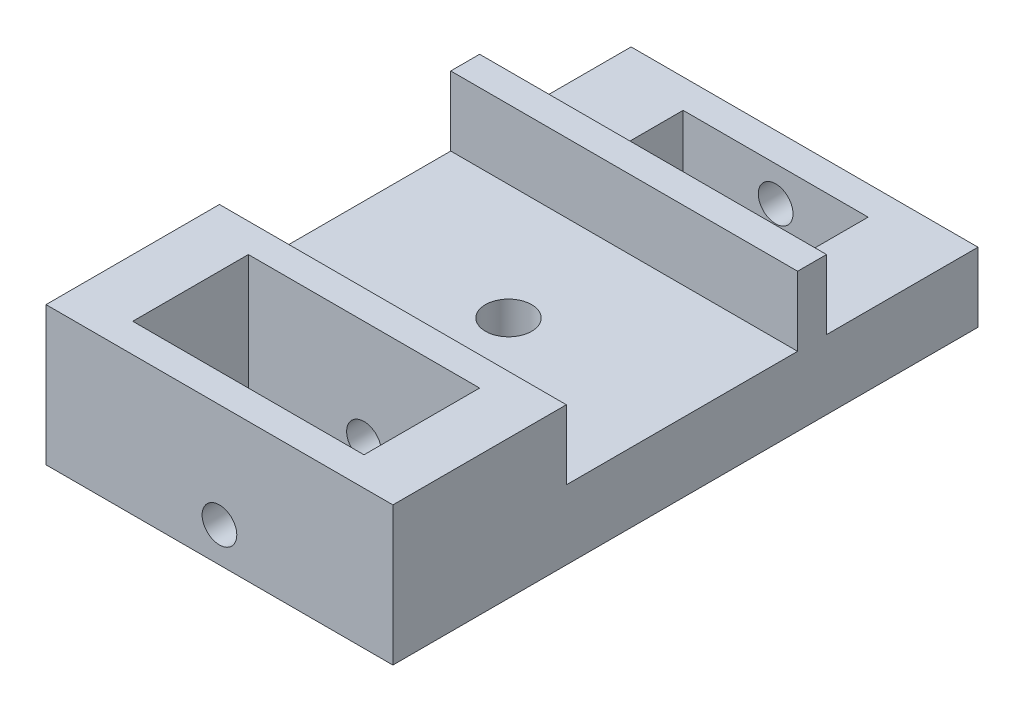
SolidWorks part; units mm, degrees
ref_plane "Front" through (0, 0, 0) normal (0, 0, 1) x (1, 0, 0)
ref_plane "Top" through (0, 0, 0) normal (0, 1, 0) x (1, 0, 0)
ref_plane "Right" through (0, 0, 0) normal (1, 0, 0) x (0, 0, -1)
sketch "Sketch1" plane through (0, 0, 0) normal (0, 1, 0) x (1, 0, 0)
  line L0 (0, -20) -> (0, -22.5)
  line L1 (0, 0) -> (-30, 0)
  line L2 (0, 0) -> (0, -20)
  line L3 (0, -20) -> (-30, -20)
  line L4 (-30, 0) -> (-30, -20)
  line L5 (0, -22.5) -> (-30, -22.5)
  line L6 (-30, -22.5) -> (-30, -20)
  line L7 (0, 0) -> (-7, 0)
  line L8 (-30, 0) -> (0, 0)
  line L9 (-30, 0) -> (-30, 2.5)
  line L10 (-30, 2.5) -> (0, 2.5)
  line L11 (0, 0) -> (0, 2.5)
  line L12 (-30, 0) -> (-23, 0)
  line L13 (-30, 2.5) -> (-30, 13.1)
  line L14 (-30, 13.1) -> (0, 13.1)
  line L15 (0, 13.1) -> (0, 2.5)
  line L16 (0, 13.1) -> (0, 15.6)
  line L17 (0, 15.6) -> (-30, 15.6)
  line L18 (-30, 15.6) -> (-30, 13.1)
  line L19 (-7, 0) -> (-7, 15.6)
  line L20 (-23, 0) -> (-23, 15.6)
  dimension "D1" = 20
  dimension "D2" = 2.5
  dimension "D3" = 2.5
  dimension "D4" = 30
  dimension "D5" = 7
  dimension "D6" = 7
  dimension "D7" = 10.6
  dimension "D8" = 2.5
extrude "Boss-Extrude1" add sketch "Sketch1" along normal blind 6 contours L1 L8 L4 L3 L2 | L6 L5 L0 L3 | L20 L1 L19 L10 | L19 L1 L11 L10 | L19 L10 L15 L14 | L19 L14 L16 L17 | L20 L14 L19 L17 | L14 L20 L17 L18 | L10 L20 L14 L13 | L8 L20 L10 L9 region at (-15, 0, 10) region at (-15, 0, 21.25) region at (-3.5, 0, -1.25) region at (-15, 0, -1.25) region at (-3.5, 0, -7.8) region at (-26.5, 0, -1.25) region at (-3.5, 0, -14.35) region at (-26.5, 0, -7.8) region at (-15, 0, -14.35) region at (-26.5, 0, -14.35)
extrude "Boss-Extrude2" add sketch "Sketch1<3>" along normal blind 12 contours L19 L1 L11 L10 | L20 L1 L19 L10 | L6 L5 L0 L3 | L8 L20 L10 L9 region at (-15, 0, 21.25) region at (-3.5, 0, -1.25) region at (-15, 0, -1.25) region at (-26.5, 0, -1.25)
sketch "Sketch1<3>" plane through (0, 0, 0) normal (0, 1, 0) x (1, 0, 0) same geometry as "Sketch1"
sketch "Sketch3" plane through (0, 0, -15.6) normal (0, 0, -1) x (-1, 0, 0)
  line L0 (30, 3) -> (23, 3)
  line L1 (30, 6) -> (30, 0) construction
  line L2 (23, 3) -> (15, 3)
  circle A0 centre (15, 3) radius 1.5
  dimension "D1" = 7
  dimension "D2" = 8
extrude "Cut-Extrude2" cut sketch "Sketch3" against normal blind 16 contours A0
ref_plane "Plane1" through (0, 0, 10) normal (0, 0, -1) x (-1, 0, 0)
sketch "Sketch2" plane through (0, 6, 0) normal (0, 1, 0) x (1, 0, 0)
  line L0 (-30, -10) -> (0, -10)
  line L1 (-30, 0) -> (-30, -20) construction
  line L2 (0, 0) -> (0, -20) construction
  circle A0 centre (-15, -10) radius 2
extrude "Cut-Extrude1" cut sketch "Sketch2" against normal through all contours L0 A0 | L0 A0 region at (-15, 6, 9.1512) region at (-15, 6, 10.8488)
sketch "Sketch5" plane through (0, 0, 0) normal (0, -1, 0) x (1, 0, 0)
  line L0 (-30, 22.5) -> (-25, 22.5)
  line L1 (-30, 22.5) -> (0, 22.5)
  line L2 (-30, 22.5) -> (-30, 32.5)
  line L3 (0, 22.5) -> (0, 32.5)
  line L4 (-30, 32.5) -> (0, 32.5)
  line L5 (-25, 22.5) -> (-25, 32.5)
  line L6 (-25, 32.5) -> (-5, 32.5)
  line L7 (-5, 32.5) -> (-5, 22.5)
  line L8 (-5, 22.5) -> (0, 22.5)
  line L9 (-30, 32.5) -> (-30, 35)
  line L10 (-30, 35) -> (0, 35)
  line L11 (0, 35) -> (0, 32.5)
  line M7 (0, 22.5) -> (-30, 22.5)
  dimension "D1" = 10
  dimension "D2" = 5
  dimension "D3" = 5
  dimension "D4" = 2.5
extrude "Boss-Extrude3" add sketch "Sketch5" against normal blind 12 contours L5 L4 L2 M7 | L11 L10 L9 L4 | L4 L7 L3 M7 region at (-27.5, 0, 27.5) region at (-15, 0, 33.75) region at (-2.5, 0, 27.5)
sketch "Sketch6" plane through (0, 0, 35) normal (0, 0, 1) x (1, 0, 0)
  line L0 (0, 0) -> (0, 6)
  line L1 (0, 12) -> (0, 0) construction
  line L2 (0, 6) -> (0, 3)
  line L3 (0, 3) -> (-15, 3)
  circle A1 centre (-15, 3) radius 1.5
extrude "Cut-Extrude4" cut sketch "Sketch6" against normal blind 20 contours A1 region at (-16.4576, 3, 35)
